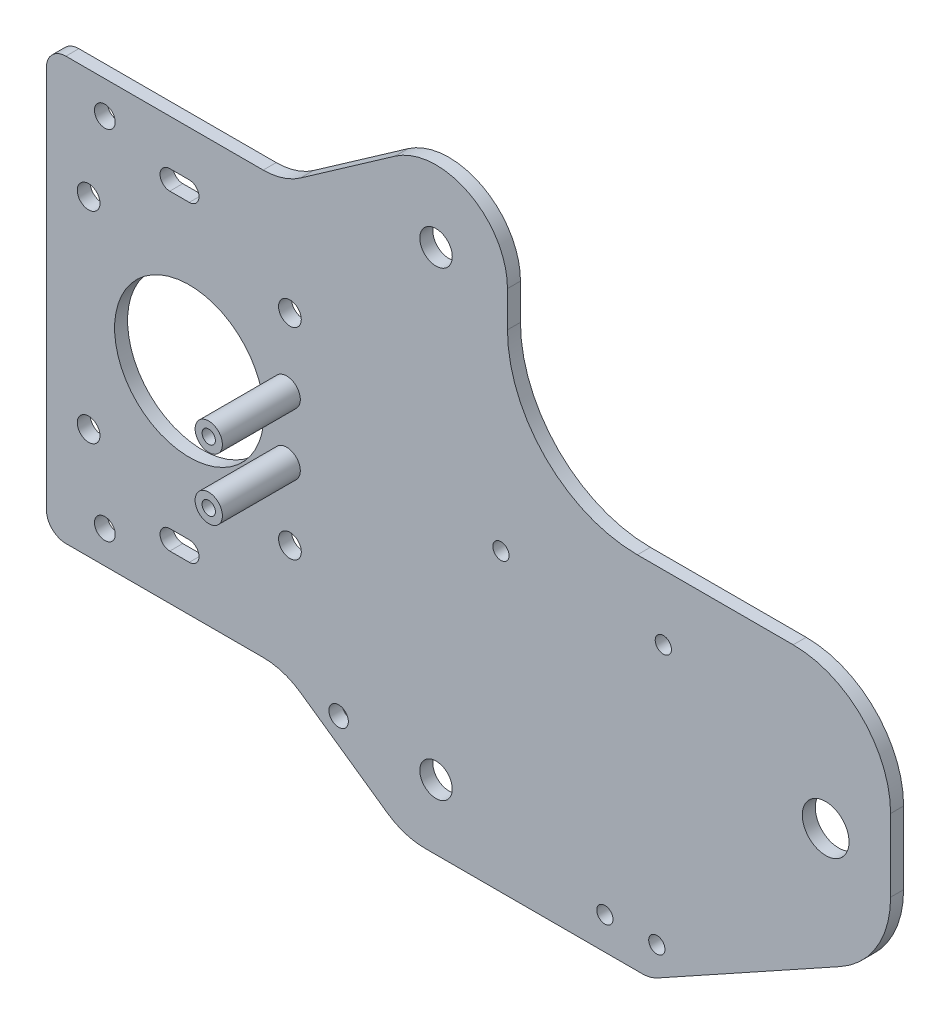
SolidWorks part; units mm, degrees
material "普通碳钢"
ref_plane "前视基准面" through (0, 0, 0) normal (0, 0, 1) x (1, 0, 0)
ref_plane "上视基准面" through (0, 0, 0) normal (0, 1, 0) x (1, 0, 0)
ref_plane "右视基准面" through (0, 0, 0) normal (1, 0, 0) x (0, 0, -1)
sketch "草图1" plane through (0, 0, 0) normal (0, 0, 1) x (1, 0, 0)
  line L0 (0, 0) -> (10948.4798, 0) construction
  line L1 (-38, 0) -> (-38, 10948.4798) construction
  line L2 (0, 0) -> (0, 50000) construction
  line L3 (-1.7434, -45.5) -> (31.7074, -45.5)
  line L4 (34.1306, -44.8736) -> (62.2696, -29.2831)
  line L5 (-6.3093, 44.5107) -> (-20.8796, 34.3085)
  line L6 (11, 35.5) -> (11, 30)
  line L7 (55, 10) -> (31, 10)
  line L8 (70, -16.1624) -> (70, -5)
  line L10 (-20.8796, -34.3085) -> (-7.4792, -43.6915)
  line L11 (-60, 29.5) -> (-60, -29.5)
  line L12 (-57, -32.5) -> (-26.6153, -32.5)
  line L13 (-57, 32.5) -> (-26.6153, 32.5)
  circle A0 centre (-38, 0) radius 11.5
  circle A1 centre (-22.5, 15.5) radius 1.75
  circle A2 centre (-22.5, -15.5) radius 1.75
  circle A3 centre (0, 35.5) radius 2.5
  circle A4 centre (0, -35.5) radius 2.5
  circle A5 centre (-53.5, -15.5) radius 1.75
  circle A6 centre (-53.5, 15.5) radius 1.75
  arc A7 (-7.4792, -43.6915) -> (-1.7434, -45.5) centre (-1.7434, -35.5) ccw
  arc A8 (70, -16.1624) -> (62.2696, -29.2831) centre (55, -16.1624) cw
  circle A9 centre (60, -12) radius 3.6
  arc A10 (11, 35.5) -> (-6.3093, 44.5107) centre (0, 35.5) ccw
  arc A11 (70, -5) -> (55, 10) centre (55, -5) ccw
  arc A12 (-20.8796, 34.3085) -> (-26.6153, 32.5) centre (-26.6153, 42.5) cw
  arc A13 (-20.8796, -34.3085) -> (-26.6153, -32.5) centre (-26.6153, -42.5) ccw
  arc A14 (-57, -32.5) -> (-60, -29.5) centre (-57, -29.5) cw
  arc A15 (-60, 29.5) -> (-57, 32.5) centre (-57, 29.5) cw
  arc A16 (11, 30) -> (31, 10) centre (31, 30) ccw
  arc A17 (31.7074, -45.5) -> (34.1306, -44.8736) centre (31.7074, -40.5) ccw
  point P30 (70, -25)
  point P43 (-4.8964, -45.5)
  point P44 (33, -45.5)
  point P59 (-41.8077, -32.5)
  dimension "D1" = 23
  dimension "D3" = 3.5
  dimension "D4" = 31
  dimension "D5" = 5
  dimension "D6" = 35.5
  dimension "D7" = 7.2
  dimension "D9" = 20
  dimension "D11" = 22
  dimension "D12" = 31
  dimension "D17" = 13
  dimension "D23" = 13
  dimension "D24" = 37
  dimension "D22" = 3
  dimension "D20" = 10
  dimension "D8" = 12
  dimension "D19" = 10
  dimension "D21" = 10
  dimension "D25" = 15
  dimension "D28" = 5
  dimension "D26" = 15
  dimension "D10" = 60
  dimension "D13" = 38
  dimension "D14" = 45.5
  dimension "D15" = 35
  dimension "D16" = 130
  dimension "D18" = 22
  dimension "D27" = 10
base flange "基体-法兰1" sketch "草图1" thickness 2 reverse thickness direction no parameters "D1"=1
hole_wizard "Ø2.5 (2.5) 直径孔1" [suppressed] positions "草图2" profile "草图3" hole size "Ø2.5" standard "GB"
sketch "草图2" plane through (0, 0, 0) normal (0, 0, 1) x (1, 0, 0)
  line L1 (-56, -32.5) -> (-26.6153, -32.5) construction
  line L2 (-59, 29.5) -> (-59, -29.5) construction
  point P0 (-56, -22.5)
  dimension "D1" = 10
  dimension "D2" = 3
sketch "草图3" plane through (-56, -22.5, 0) normal (1, 0, 0) x (0, -1, 0)
  line L0 (0, 0) -> (0, 2)
  line L1 (0, 2) -> (1.25, 2)
  line L2 (1.25, 2) -> (1.25, 0)
  line L5 (1.25, 0) -> (0, 0)
  line L11 (0, -6.35) -> (0, 107.95) construction
  dimension "通孔孔直径" = 2.5
  dimension "通孔孔深度" = 2
sketch "草图4" plane through (0, 0, -2) normal (0, 0, -1) x (-1, 0, 0)
  line L0 (200000, 0) -> (-210948.4798, 0) construction
  line L1 (200000, 0) -> (-210948.4798, 0) construction
  circle A0 centre (-10, 0) radius 3.25
  circle A1 centre (-35, 0) radius 3.25
  circle A2 centre (0, 35.5) radius 2.5 construction
  dimension "D3" = 6.5
  dimension "D1" = 10
  dimension "D2" = 25
extrude "凸台-拉伸1" add sketch "草图4" along normal blind 2
hole_wizard "M3 螺纹孔2" positions "草图5" profile "草图6" tap size "M3" standard "GB" end condition up to next
sketch "草图5" plane through (0, 0, 0) normal (0, 0, -1) x (-1, 0, 0)
  point P0 (-10, 0)
  point P3 (-35, 0)
sketch "草图6" plane through (10, 0, 0) normal (1, 0, 0) x (0, -1, 0)
  line L0 (0, 0) -> (0, 4)
  line L1 (0, 4) -> (1.25, 4)
  line L2 (1.25, 4) -> (1.25, 0)
  line L5 (1.25, 0) -> (0, 0)
  line L11 (0, -6.35) -> (0, 107.95) construction
  dimension "通孔螺纹孔钻头直径" = 2.5
  dimension "通孔螺纹孔钻头深度" = 4
cosmetic thread "孔螺蚊线9"
cosmetic thread "孔螺蚊线10"
sketch "草图7" plane through (0, 0, 0) normal (0, 0, 1) x (1, 0, 0)
  line L0 (-38, -200000) -> (-38, 210948.4798) construction
  line L1 (-200000, 0) -> (210948.4798, 0) construction
  line L2 (-38, -200000) -> (-38, 210948.4798)
  line L3 (-200000, 0) -> (210948.4798, 0)
  line L4 (-38, 24) -> (-41, 24) construction
  line L5 (-38, 22.5) -> (-41, 22.5)
  line L6 (-38, 25.5) -> (-41, 25.5)
  line L7 (-38, -24) -> (-41, -24) construction
  line L8 (-38, -25.5) -> (-41, -25.5)
  line L9 (-38, -22.5) -> (-41, -22.5)
  circle A0 centre (-38, 24) radius 3.25 construction
  circle A1 centre (-38, -24) radius 3.25 construction
  circle A2 centre (-38, 0) radius 11.5 construction
  arc A3 (-38, 22.5) -> (-38, 25.5) centre (-38, 24) ccw
  arc A4 (-41, 25.5) -> (-41, 22.5) centre (-41, 24) ccw
  arc A5 (-38, -25.5) -> (-38, -22.5) centre (-38, -24) ccw
  arc A6 (-41, -22.5) -> (-41, -25.5) centre (-41, -24) ccw
  point P8 (-39.5, 24)
  point P13 (-39.5, -24)
  dimension "D1" = 6.5
  dimension "D2" = 6.5
  dimension "D5" = 1.5
  dimension "D8" = 1.5
  dimension "D3" = 24
  dimension "D4" = 24
  dimension "D6" = 3
  dimension "D7" = 3
extrude "切除-拉伸1" cut sketch "草图7" against normal up to next normal cut yes
sketch "草图8" plane through (0, 0, 0) normal (0, 0, 1) x (1, 0, 0)
  circle A0 centre (-23, 4.75) radius 2.1
  circle A1 centre (-23, -4.75) radius 2.1
  circle A2 centre (-38, 0) radius 11.5 construction
  dimension "D4" = 4.2
  dimension "D1" = 9.5
  dimension "D2" = 15
  dimension "D3" = 4.75
extrude "凸台-拉伸2" add sketch "草图8" along normal blind 12
hole_wizard "M2.5 螺纹孔1" positions "草图9" profile "草图10" tap size "M2.5" standard "GB"
sketch "草图9" plane through (0, 0, 12) normal (0, 0, 1) x (1, 0, 0)
  point P0 (-23, 4.75)
  point P3 (-23, -4.75)
sketch "草图10" plane through (-23, 4.75, 12) normal (1, 0, 0) x (0, -1, 0)
  line L0 (0, 0) -> (0, 10)
  line L1 (0, 10) -> (1.025, 10)
  line L2 (1.025, 10) -> (1.025, 0)
  line L5 (1.025, 0) -> (0, 0)
  line L10 (0, 10) -> (-1.025, 10) construction
  line L11 (0, -6.35) -> (0, 107.95) construction
  dimension "螺纹孔钻头直径" = 2.05
  dimension "螺纹孔钻头深度" = 10
  dimension "导头角度" = 180
cosmetic thread "孔螺蚊线3"
cosmetic thread "孔螺蚊线4"
sketch "草图11" plane through (0, 0, 0) normal (0, 0, 1) x (1, 0, 0)
  line L0 (-60, 29.5) -> (-60, -29.5) construction
  line L1 (-26.6153, 32.5) -> (-57, 32.5) construction
  line L2 (-57, -32.5) -> (-26.6153, -32.5) construction
  circle A0 centre (-51, 27.5) radius 1.6
  circle A1 centre (-51, -27.5) radius 1.6
  dimension "D1" = 3.2
  dimension "D2" = 9
  dimension "D3" = 5
  dimension "D4" = 5
  dimension "D5" = 9
extrude "切除-拉伸2" cut sketch "草图11" against normal up to next normal cut yes
sketch "草图12" plane through (0, 0, -2) normal (0, 0, 1) x (1, 0, 0)
  line L0 (-1.7434, -45.5) -> (31.7074, -45.5) construction
  circle A0 centre (26, -40.5) radius 3.25
  circle A1 centre (34, -40.5) radius 3.25
  circle A2 centre (0, -35.5) radius 2.5 construction
  dimension "D2" = 6.5
  dimension "D1" = 8
  dimension "D3" = 26
  dimension "D4" = 5
extrude "凸台-拉伸3" add sketch "草图12" against normal blind 2
hole_wizard "M3 螺纹孔3" positions "草图13" profile "草图14" tap size "M3" standard "GB" end condition up to next
sketch "草图13" plane through (0, 0, 0) normal (0, 0, -1) x (-1, 0, 0)
  point P0 (-34, -40.5)
  point P3 (-26, -40.5)
sketch "草图14" plane through (34, -40.5, 0) normal (1, 0, 0) x (0, -1, 0)
  line L0 (0, 0) -> (0, 4)
  line L1 (0, 4) -> (1.25, 4)
  line L2 (1.25, 4) -> (1.25, 0)
  line L5 (1.25, 0) -> (0, 0)
  line L11 (0, -6.35) -> (0, 107.95) construction
  dimension "通孔螺纹孔钻头直径" = 2.5
  dimension "通孔螺纹孔钻头深度" = 4
cosmetic thread "孔螺蚊线7"
cosmetic thread "孔螺蚊线8"
sketch "草图15" plane through (0, 0, -2) normal (0, 0, -1) x (-1, 0, 0)
  line L0 (57, -32.5) -> (26.6153, -32.5) construction
  line L1 (60, 29.5) -> (60, -29.5) construction
  circle A0 centre (15, -34.5) radius 1.5
  dimension "D1" = 3
  dimension "D2" = 2
  dimension "D3" = 45
extrude "切除-拉伸3" cut sketch "草图15" against normal up to next normal cut yes
sketch "折弯-线1" [suppressed] plane through (0, 0, 0) normal (0, 1, 0) x (1, 0, 0)
sketch "边界框1" [suppressed] plane through (0, 0, 0) normal (0, 1, 0) x (1, 0, 0)
sheet metal parameters "钣金9" thickness 2 parameters "D1"=2
flat pattern "平板型式9" [suppressed]
sketch "折弯-线2" plane through (0, 0, 0) normal (0, 1, 0) x (1, 0, 0)
sketch "边界框2" [suppressed] plane through (0, 0, 0) normal (0, 1, 0) x (1, 0, 0)
sheet metal parameters "钣金11" thickness 2 parameters "D1"=2
flat pattern "平板型式9"
sketch "折弯-线2" plane through (0, 0, 0) normal (0, 1, 0) x (1, 0, 0)
sketch "边界框2" [suppressed] plane through (0, 0, 0) normal (0, 1, 0) x (1, 0, 0)
sheet metal parameters "钣金12" thickness 2 parameters "D1"=2
flat pattern "平板型式9"
sketch "折弯-线2" plane through (0, 0, 0) normal (0, 1, 0) x (1, 0, 0)
sketch "边界框2" [suppressed] plane through (0, 0, 0) normal (0, 1, 0) x (1, 0, 0)
sheet metal parameters "钣金13" thickness 2 parameters "D1"=2
flat pattern "平板型式9"
sketch "折弯-线2" plane through (0, 0, 0) normal (0, 1, 0) x (1, 0, 0)
sketch "边界框2" [suppressed] plane through (0, 0, 0) normal (0, 1, 0) x (1, 0, 0)
sheet metal parameters "钣金16" thickness 2 parameters "D1"=2
flat pattern "平板型式9"
sketch "折弯-线2" plane through (0, 0, 0) normal (0, 1, 0) x (1, 0, 0)
sketch "边界框2" [suppressed] plane through (0, 0, 0) normal (0, 1, 0) x (1, 0, 0)
sheet metal parameters "钣金17" thickness 2 parameters "D1"=2
flat pattern "平板型式9"
sketch "折弯-线2" plane through (0, 0, 0) normal (0, 1, 0) x (1, 0, 0)
sketch "边界框2" [suppressed] plane through (0, 0, 0) normal (0, 1, 0) x (1, 0, 0)
sheet metal parameters "钣金18" thickness 2 parameters "D1"=2
flat pattern "平板型式9"
sketch "折弯-线2" plane through (0, 0, 0) normal (0, 1, 0) x (1, 0, 0)
sketch "边界框2" [suppressed] plane through (0, 0, 0) normal (0, 1, 0) x (1, 0, 0)
sheet metal parameters "钣金19" thickness 2 parameters "D1"=2
flat pattern "平板型式9"
sketch "折弯-线2" plane through (0, 0, 0) normal (0, 1, 0) x (1, 0, 0)
sketch "边界框2" [suppressed] plane through (0, 0, 0) normal (0, 1, 0) x (1, 0, 0)
sheet metal parameters "钣金21" thickness 2 parameters "D1"=2
flat pattern "平板型式9"
sketch "折弯-线2" plane through (0, 0, 0) normal (0, 1, 0) x (1, 0, 0)
sketch "边界框2" [suppressed] plane through (0, 0, 0) normal (0, 1, 0) x (1, 0, 0)
sheet metal parameters "钣金22" thickness 2 parameters "D1"=2
flat pattern "平板型式9"
sketch "折弯-线2" plane through (0, 0, 0) normal (0, 1, 0) x (1, 0, 0)
sketch3d "边界框2" [suppressed]
  line L0 (-115, -29.3376, 0) -> (15, -29.3376, 0) construction
  line L1 (-115, 62.6623, 0) -> (15, 62.6623, 0) construction
  line L2 (-115, -29.3376, 0) -> (-115, 62.6623, 0) construction
  line L3 (15, -29.3376, 0) -> (15, 62.6623, 0) construction
sheet metal parameters "钣金23" thickness 2 parameters "D1"=2
flat pattern "平板型式9"
sketch "折弯-线2" plane through (0, 0, 0) normal (0, 1, 0) x (1, 0, 0)
sketch3d "边界框2" [suppressed]
  line L0 (-115, -29.3376, 0) -> (15, -29.3376, 0) construction
  line L1 (-115, 62.6623, 0) -> (15, 62.6623, 0) construction
  line L2 (-115, -29.3376, 0) -> (-115, 62.6623, 0) construction
  line L3 (15, -29.3376, 0) -> (15, 62.6623, 0) construction
